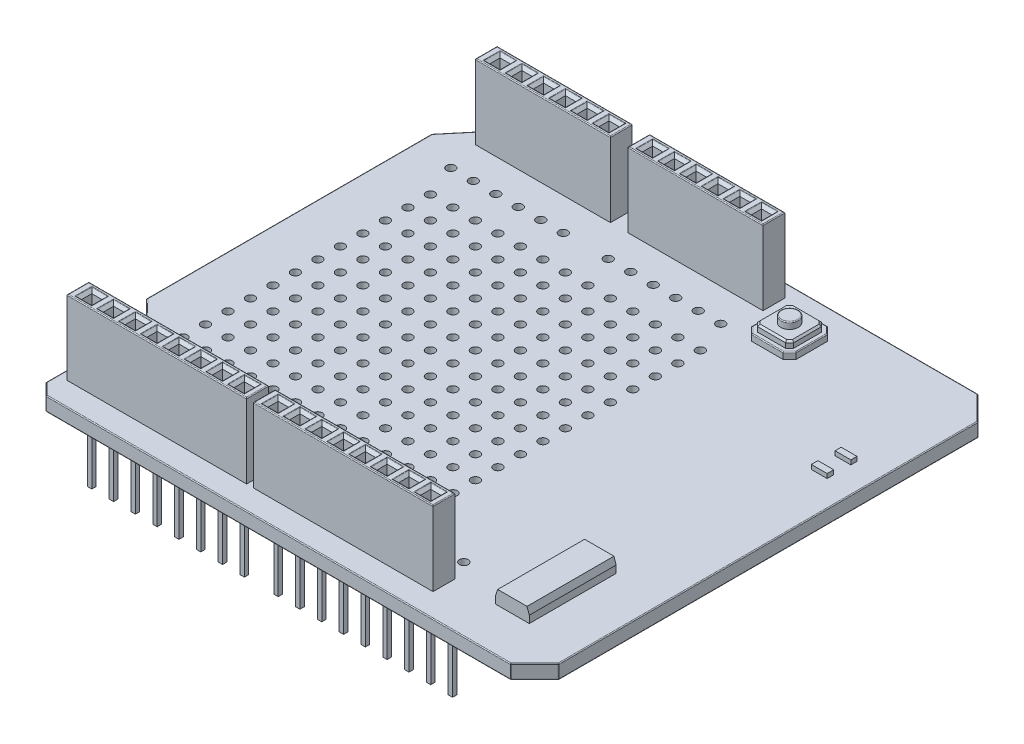
SolidWorks part; units mm, degrees
ref_plane "Front Plane" through (0, 0, 0) normal (0, 0, 1) x (1, 0, 0)
ref_plane "Top Plane" through (0, 0, 0) normal (0, 1, 0) x (1, 0, 0)
ref_plane "Right Plane" through (0, 0, 0) normal (1, 0, 0) x (0, 0, -1)
sketch "Sketch1" plane through (0, 0, 0) normal (0, 1, 0) x (1, 0, 0)
  line L1 (-29.955, 26.8) -> (29.955, 26.8)
  line L2 (-29.955, 26.8) -> (-29.955, -26.8)
  line L3 (-29.955, -26.8) -> (29.955, -26.8)
  line L4 (29.955, 26.8) -> (29.955, -26.8)
  line L5 (-29.955, 26.8) -> (29.955, -26.8) construction
  line L6 (-29.955, -26.8) -> (29.955, 26.8) construction
  point P0 (0, 0)
  dimension "D1" = 59.91
  dimension "D2" = 53.6
extrude "Boss-Extrude1" add sketch "Sketch1" along normal blind 1.63
sketch "Sketch2" plane through (0, 1.63, 0) normal (0, 1, 0) x (1, 0, 0)
  line L0 (29.955, 26.8) -> (-29.955, 26.8) construction
  line L1 (-26.385, 25.23) -> (-10.885, 25.23)
  line L2 (-26.385, 25.23) -> (-26.385, 22.73)
  line L3 (-26.385, 22.73) -> (-10.885, 22.73)
  line L4 (-10.885, 25.23) -> (-10.885, 22.73)
  line L5 (-26.385, 25.23) -> (-10.885, 22.73) construction
  line L6 (-26.385, 22.73) -> (-10.885, 25.23) construction
  line L7 (-29.955, 26.8) -> (-29.955, -26.8) construction
  line L8 (-8.885, 25.23) -> (-8.885, 22.73)
  line L9 (-8.885, 25.23) -> (6.615, 25.23)
  line L10 (6.615, 25.23) -> (6.615, 22.73)
  line L11 (-8.885, 22.73) -> (6.615, 22.73)
  line L12 (-26.385, 25.23) -> (-8.885, 25.23) construction
  line L13 (15.595, -21.5984) -> (15.595, -24.0984)
  line L14 (-26.385, -21.5984) -> (-5.785, -21.5984)
  line L15 (-26.385, -21.5984) -> (-26.385, -24.0984)
  line L16 (-26.385, -24.0984) -> (-5.785, -24.0984)
  line L17 (-5.785, -21.5984) -> (-5.785, -24.0984)
  line L18 (-26.385, -21.5984) -> (-5.785, -24.0984) construction
  line L19 (-26.385, -24.0984) -> (-5.785, -21.5984) construction
  line L20 (-5.005, -21.5984) -> (15.595, -21.5984)
  line L21 (-5.005, -24.0984) -> (15.595, -24.0984)
  line L22 (-5.005, -21.5984) -> (-5.005, -24.0984)
  point P0 (-18.635, 23.98)
  point P9 (-16.085, -22.8484)
  dimension "D1" = 15.5
  dimension "D2" = 2.5
  dimension "D3" = 1.57
  dimension "D4" = 3.57
  dimension "D6" = 17.5
  dimension "D7" = 2.5
  dimension "D8" = 20.6
  dimension "D9" = 3.57
  dimension "D10" = 2
  dimension "D5" = 2
extrude "Boss-Extrude2" add sketch "Sketch2" along normal blind 8.54
sketch "Sketch3" plane through (0, 1.63, 0) normal (0, 1, 0) x (1, 0, 0)
  line L0 (29.955, 26.8) -> (-29.955, 26.8) construction
  line L1 (8.995, 24.15) -> (12.605, 24.15)
  line L2 (8.245, 23.4) -> (8.245, 19.79)
  line L3 (8.995, 19.04) -> (12.605, 19.04)
  line L4 (13.355, 23.4) -> (13.355, 19.79)
  line L5 (8.245, 24.15) -> (13.355, 19.04) construction
  line L6 (8.245, 19.04) -> (13.355, 24.15) construction
  line L7 (29.955, -26.8) -> (29.955, 26.8) construction
  line L8 (12.605, 24.15) -> (13.355, 23.4)
  line L9 (8.245, 23.4) -> (8.995, 24.15)
  line L10 (8.245, 19.79) -> (8.995, 19.04)
  line L11 (12.605, 19.04) -> (13.355, 19.79)
  point P0 (10.8, 21.595)
  dimension "D1" = 5.11
  dimension "D2" = 5.11
  dimension "D3" = 2.65
  dimension "D4" = 16.6
  dimension "D5" = 0.75
  dimension "D6" = 45
  dimension "D7" = 0.75
  dimension "D8" = 45
  dimension "D9" = 0.75
  dimension "D10" = 45
  dimension "D11" = 0.75
  dimension "D12" = 45
extrude "Boss-Extrude3" add sketch "Sketch3" along normal blind 0.75
sketch "Sketch4" plane through (0, 2.38, 0) normal (0, 1, 0) x (1, 0, 0)
  line L47 (8.745, 19.9971) -> (9.3486, 19.3936)
  line L48 (8.745, 23.1929) -> (8.745, 19.9971)
  line L49 (9.2021, 23.65) -> (8.745, 23.1929)
  line L50 (12.605, 23.65) -> (9.2021, 23.65)
  line L51 (8.745, 19.9971) -> (9.2021, 19.54)
  line L52 (8.745, 23.1929) -> (8.745, 19.9971)
  line L53 (9.2021, 23.65) -> (8.745, 23.1929)
  line L54 (12.3979, 23.65) -> (9.2021, 23.65)
  line L65 (12.855, 23.1929) -> (12.2514, 23.7964)
  line L66 (12.855, 19.9971) -> (12.855, 23.1929)
  line L67 (12.3979, 19.54) -> (12.855, 19.9971)
  line L68 (8.995, 19.54) -> (12.3979, 19.54)
  line L69 (12.855, 23.1929) -> (12.3979, 23.65)
  line L70 (12.855, 19.9971) -> (12.855, 23.1929)
  line L71 (12.3979, 19.54) -> (12.855, 19.9971)
  line L72 (9.2021, 19.54) -> (12.3979, 19.54)
  dimension "D1" = 0.5
  dimension "D2" = 0.5
extrude "Boss-Extrude4" add sketch "Sketch4" along normal blind 0.75
sketch "Sketch5" plane through (0, 3.13, 0) normal (0, 1, 0) x (1, 0, 0)
  circle A0 centre (10.8, 21.595) radius 1
  dimension "D1" = 2
extrude "Boss-Extrude5" add sketch "Sketch5" along normal blind 0.75
chamfer "Chamfer1" distance 0.2 angle 45 8 edges at (8.9736, 3.13, -23.4214) (10.8, 3.13, -23.65) (12.6264, 3.13, -23.4214) (8.745, 3.13, -21.595) (8.9736, 3.13, -19.7686) (10.8, 3.13, -19.54) (12.6264, 3.13, -19.7686) (12.855, 3.13, -21.595)
fillet "Fillet1" radius 0.1 1 edges at (10.8, 3.88, -20.595)
fillet "Fillet2" radius 0.1 8 edges at (8.62, 2.38, -19.415) (8.245, 2.38, -21.595) (8.62, 2.38, -23.775) (10.8, 2.38, -24.15) (12.98, 2.38, -23.775) (10.8, 2.38, -19.04) (12.98, 2.38, -19.415) (13.355, 2.38, -21.595)
sketch "Sketch6" plane through (0, 1.63, 0) normal (0, 1, 0) x (1, 0, 0)
  line L0 (29.955, -26.8) -> (29.955, 26.8) construction
  line L1 (20.405, -11.78) -> (24.285, -11.78)
  line L2 (20.405, -11.78) -> (20.405, -21.75)
  line L3 (20.405, -21.75) -> (24.285, -21.75)
  line L4 (24.285, -11.78) -> (24.285, -21.75)
  line L5 (20.405, -11.78) -> (24.285, -21.75) construction
  line L6 (20.405, -21.75) -> (24.285, -11.78) construction
  line L7 (-29.955, -26.8) -> (29.955, -26.8) construction
  point P0 (22.345, -16.765)
  dimension "D1" = 3.88
  dimension "D2" = 9.97
  dimension "D3" = 5.67
  dimension "D4" = 5.05
extrude "Boss-Extrude6" add sketch "Sketch6" along normal blind 1.58
chamfer "Chamfer2" distance 0.75 angle 19 2 edges at (20.405, 3.21, 16.765) (24.285, 3.21, 16.765) first distance on face at (20.405, 2.42, 16.765) first distance on face at (24.285, 2.42, 16.765)
sketch "Sketch7" plane through (0, 10.17, 0) normal (0, 1, 0) x (1, 0, 0)
  line L0 (-26.385, 25.23) -> (-26.385, 22.73) construction
  line L1 (-25.385, 24.57) -> (-24.205, 24.57)
  line L2 (-25.385, 24.57) -> (-25.385, 23.39)
  line L3 (-25.385, 23.39) -> (-24.205, 23.39)
  line L4 (-24.205, 24.57) -> (-24.205, 23.39)
  line L5 (-25.385, 24.57) -> (-24.205, 23.39) construction
  line L6 (-25.385, 23.39) -> (-24.205, 24.57) construction
  line L7 (-26.385, 23.98) -> (-25.385, 23.98) construction
  line L8 (-22.885, 24.57) -> (-22.885, 23.39)
  line L9 (-22.885, 24.57) -> (-21.705, 24.57)
  line L10 (-21.705, 24.57) -> (-21.705, 23.39)
  line L11 (-22.885, 23.39) -> (-21.705, 23.39)
  line L12 (-20.385, 24.57) -> (-20.385, 23.39)
  line L13 (-20.385, 24.57) -> (-19.205, 24.57)
  line L14 (-19.205, 24.57) -> (-19.205, 23.39)
  line L15 (-20.385, 23.39) -> (-19.205, 23.39)
  line L16 (-17.885, 24.57) -> (-17.885, 23.39)
  line L17 (-17.885, 24.57) -> (-16.705, 24.57)
  line L18 (-16.705, 24.57) -> (-16.705, 23.39)
  line L19 (-17.885, 23.39) -> (-16.705, 23.39)
  line L20 (-15.385, 24.57) -> (-15.385, 23.39)
  line L21 (-15.385, 24.57) -> (-14.205, 24.57)
  line L22 (-14.205, 24.57) -> (-14.205, 23.39)
  line L23 (-15.385, 23.39) -> (-14.205, 23.39)
  line L24 (-12.885, 24.57) -> (-12.885, 23.39)
  line L25 (-12.885, 24.57) -> (-11.705, 24.57)
  line L26 (-11.705, 24.57) -> (-11.705, 23.39)
  line L27 (-12.885, 23.39) -> (-11.705, 23.39)
  line L28 (-26.385, -21.5984) -> (-26.385, -24.0984) construction
  line L29 (-25.385, -22.2584) -> (-24.205, -22.2584)
  line L30 (-25.385, -22.2584) -> (-25.385, -23.4384)
  line L31 (-25.385, -23.4384) -> (-24.205, -23.4384)
  line L32 (-7.885, 24.57) -> (-7.885, 23.39)
  line L33 (-7.885, 24.57) -> (-6.705, 24.57)
  line L34 (-6.705, 24.57) -> (-6.705, 23.39)
  line L35 (-7.885, 23.39) -> (-6.705, 23.39)
  line L36 (-5.385, 24.57) -> (-5.385, 23.39)
  line L37 (-5.385, 24.57) -> (-4.205, 24.57)
  line L38 (-4.205, 24.57) -> (-4.205, 23.39)
  line L39 (-5.385, 23.39) -> (-4.205, 23.39)
  line L40 (-2.885, 24.57) -> (-2.885, 23.39)
  line L41 (-2.885, 24.57) -> (-1.705, 24.57)
  line L42 (-1.705, 24.57) -> (-1.705, 23.39)
  line L43 (-2.885, 23.39) -> (-1.705, 23.39)
  line L44 (-0.385, 24.57) -> (-0.385, 23.39)
  line L45 (-0.385, 24.57) -> (0.795, 24.57)
  line L46 (0.795, 24.57) -> (0.795, 23.39)
  line L47 (-0.385, 23.39) -> (0.795, 23.39)
  line L48 (2.115, 24.57) -> (2.115, 23.39)
  line L49 (2.115, 24.57) -> (3.295, 24.57)
  line L50 (3.295, 24.57) -> (3.295, 23.39)
  line L51 (2.115, 23.39) -> (3.295, 23.39)
  line L52 (4.615, 24.57) -> (4.615, 23.39)
  line L53 (4.615, 24.57) -> (5.795, 24.57)
  line L54 (5.795, 24.57) -> (5.795, 23.39)
  line L55 (4.615, 23.39) -> (5.795, 23.39)
  line L56 (-10.385, 24.57) -> (-9.205, 24.57)
  line L57 (-9.205, 24.57) -> (-9.205, 23.39)
  line L58 (-10.385, 23.39) -> (-9.205, 23.39)
  line L59 (-10.385, 24.57) -> (-10.385, 23.39)
  line L60 (-24.205, -22.2584) -> (-24.205, -23.4384)
  line L61 (-25.385, -22.2584) -> (-24.205, -23.4384) construction
  line L62 (-25.385, -23.4384) -> (-24.205, -22.2584) construction
  line L63 (-26.385, -22.8484) -> (-25.385, -22.8484) construction
  line L64 (-26.385, -21.5984) -> (-26.385, -24.0984) construction
  line L65 (-21.705, -22.2584) -> (-21.705, -23.4384)
  line L66 (-22.885, -22.2584) -> (-21.705, -22.2584)
  line L67 (-22.885, -23.4384) -> (-21.705, -23.4384)
  line L68 (-22.885, -22.2584) -> (-22.885, -23.4384)
  line L69 (-19.205, -22.2584) -> (-19.205, -23.4384)
  line L70 (-20.385, -22.2584) -> (-19.205, -22.2584)
  line L71 (-20.385, -23.4384) -> (-19.205, -23.4384)
  line L72 (-20.385, -22.2584) -> (-20.385, -23.4384)
  line L73 (-16.705, -22.2584) -> (-16.705, -23.4384)
  line L74 (-17.885, -22.2584) -> (-16.705, -22.2584)
  line L75 (-17.885, -23.4384) -> (-16.705, -23.4384)
  line L76 (-17.885, -22.2584) -> (-17.885, -23.4384)
  line L77 (-14.205, -22.2584) -> (-14.205, -23.4384)
  line L78 (-15.385, -22.2584) -> (-14.205, -22.2584)
  line L79 (-15.385, -23.4384) -> (-14.205, -23.4384)
  line L80 (-15.385, -22.2584) -> (-15.385, -23.4384)
  line L81 (-11.705, -22.2584) -> (-11.705, -23.4384)
  line L82 (-12.885, -22.2584) -> (-11.705, -22.2584)
  line L83 (-12.885, -23.4384) -> (-11.705, -23.4384)
  line L84 (-12.885, -22.2584) -> (-12.885, -23.4384)
  line L85 (-9.205, -22.2584) -> (-9.205, -23.4384)
  line L86 (-10.385, -22.2584) -> (-9.205, -22.2584)
  line L87 (-10.385, -23.4384) -> (-9.205, -23.4384)
  line L88 (-10.385, -22.2584) -> (-10.385, -23.4384)
  line L89 (-6.705, -22.2584) -> (-6.705, -23.4384)
  line L90 (-7.885, -22.2584) -> (-6.705, -22.2584)
  line L91 (-7.885, -23.4384) -> (-6.705, -23.4384)
  line L92 (-7.885, -22.2584) -> (-7.885, -23.4384)
  line L93 (-5.005, -21.5984) -> (-5.005, -24.0984) construction
  line L94 (-4.005, -22.2584) -> (-2.825, -22.2584)
  line L95 (-4.005, -22.2584) -> (-4.005, -23.4384)
  line L96 (-4.005, -23.4384) -> (-2.825, -23.4384)
  line L97 (-2.825, -22.2584) -> (-2.825, -23.4384)
  line L98 (-4.005, -22.2584) -> (-2.825, -23.4384) construction
  line L99 (-4.005, -23.4384) -> (-2.825, -22.2584) construction
  line L100 (-4.005, -22.8484) -> (-5.005, -22.8484) construction
  line L101 (-5.005, -21.5984) -> (-5.005, -24.0984) construction
  line L102 (-1.505, -22.8484) -> (-2.505, -22.8484) construction
  line L103 (-0.325, -22.2584) -> (-0.325, -23.4384)
  line L104 (-1.505, -22.2584) -> (-0.325, -22.2584)
  line L105 (-1.505, -23.4384) -> (-0.325, -23.4384)
  line L106 (-1.505, -22.2584) -> (-1.505, -23.4384)
  line L107 (0.995, -22.8484) -> (-0.005, -22.8484) construction
  line L108 (2.175, -22.2584) -> (2.175, -23.4384)
  line L109 (0.995, -22.2584) -> (2.175, -22.2584)
  line L110 (0.995, -23.4384) -> (2.175, -23.4384)
  line L111 (0.995, -22.2584) -> (0.995, -23.4384)
  line L112 (3.495, -22.8484) -> (2.495, -22.8484) construction
  line L113 (4.675, -22.2584) -> (4.675, -23.4384)
  line L114 (3.495, -22.2584) -> (4.675, -22.2584)
  line L115 (3.495, -23.4384) -> (4.675, -23.4384)
  line L116 (3.495, -22.2584) -> (3.495, -23.4384)
  line L117 (5.995, -22.8484) -> (4.995, -22.8484) construction
  line L118 (7.175, -22.2584) -> (7.175, -23.4384)
  line L119 (5.995, -22.2584) -> (7.175, -22.2584)
  line L120 (5.995, -23.4384) -> (7.175, -23.4384)
  line L121 (5.995, -22.2584) -> (5.995, -23.4384)
  line L122 (8.495, -22.8484) -> (7.495, -22.8484) construction
  line L123 (9.675, -22.2584) -> (9.675, -23.4384)
  line L124 (8.495, -22.2584) -> (9.675, -22.2584)
  line L125 (8.495, -23.4384) -> (9.675, -23.4384)
  line L126 (8.495, -22.2584) -> (8.495, -23.4384)
  line L127 (10.995, -22.8484) -> (9.995, -22.8484) construction
  line L128 (12.175, -22.2584) -> (12.175, -23.4384)
  line L129 (10.995, -22.2584) -> (12.175, -22.2584)
  line L130 (10.995, -23.4384) -> (12.175, -23.4384)
  line L131 (10.995, -22.2584) -> (10.995, -23.4384)
  line L132 (13.495, -22.8484) -> (12.495, -22.8484) construction
  line L133 (14.675, -22.2584) -> (14.675, -23.4384)
  line L134 (13.495, -22.2584) -> (14.675, -22.2584)
  line L135 (13.495, -23.4384) -> (14.675, -23.4384)
  line L136 (13.495, -22.2584) -> (13.495, -23.4384)
  line L137 (-4.005, -22.8484) -> (-1.505, -22.8484) construction
  point P0 (-24.795, 23.98)
  point P5 (-26.385, 23.98)
  point P10 (-24.795, -22.8484)
  point P73 (-3.415, -22.8484)
  dimension "D1" = 1.18
  dimension "D2" = 1.18
  dimension "D3" = 1
  dimension "D5" = 1.18
  dimension "D6" = 1.18
  dimension "D7" = 1
  dimension "D9" = 1.18
  dimension "D10" = 1.18
  dimension "D11" = 1
  dimension "D13" = 2.5
  dimension "D4" = 13
  dimension "D8" = 8
  dimension "D12" = 8
extrude "Cut-Extrude1" cut sketch "Sketch7" against normal blind 6.58
chamfer "Chamfer3" distance 0.35 angle 45 112 edges at (-24.795, 10.17, -23.39) (-24.205, 10.17, -23.98) (-25.385, 10.17, -23.98) (-24.795, 10.17, -24.57) (14.085, 10.17, 23.4384) (14.675, 10.17, 22.8484) (13.495, 10.17, 22.8484) (14.085, 10.17, 22.2584) (11.585, 10.17, 23.4384) (12.175, 10.17, 22.8484) (10.995, 10.17, 22.8484) (11.585, 10.17, 22.2584) (9.085, 10.17, 23.4384) (9.675, 10.17, 22.8484) (8.495, 10.17, 22.8484) (9.085, 10.17, 22.2584) (6.585, 10.17, 23.4384) (7.175, 10.17, 22.8484) (5.995, 10.17, 22.8484) (6.585, 10.17, 22.2584) (4.085, 10.17, 23.4384) (4.675, 10.17, 22.8484) (3.495, 10.17, 22.8484) (4.085, 10.17, 22.2584) (1.585, 10.17, 23.4384) (2.175, 10.17, 22.8484) (0.995, 10.17, 22.8484) (1.585, 10.17, 22.2584) (-0.915, 10.17, 23.4384) (-0.325, 10.17, 22.8484) (-1.505, 10.17, 22.8484) (-0.915, 10.17, 22.2584) (-3.415, 10.17, 23.4384) (-2.825, 10.17, 22.8484) (-4.005, 10.17, 22.8484) (-3.415, 10.17, 22.2584) (-7.295, 10.17, 23.4384) (-7.885, 10.17, 22.8484) (-6.705, 10.17, 22.8484) (-7.295, 10.17, 22.2584) (-9.795, 10.17, 23.4384) (-10.385, 10.17, 22.8484) (-9.205, 10.17, 22.8484) (-9.795, 10.17, 22.2584) (-12.295, 10.17, 23.4384) (-12.885, 10.17, 22.8484) (-11.705, 10.17, 22.8484) (-12.295, 10.17, 22.2584) (-14.795, 10.17, 23.4384) (-15.385, 10.17, 22.8484) (-14.205, 10.17, 22.8484) (-14.795, 10.17, 22.2584) (-17.295, 10.17, 23.4384) (-17.885, 10.17, 22.8484) (-16.705, 10.17, 22.8484) (-17.295, 10.17, 22.2584) (-19.795, 10.17, 23.4384) (-20.385, 10.17, 22.8484) (-19.205, 10.17, 22.8484) (-19.795, 10.17, 22.2584) (-22.295, 10.17, 23.4384) (-22.885, 10.17, 22.8484) (-21.705, 10.17, 22.8484) (-22.295, 10.17, 22.2584) (-24.795, 10.17, 23.4384) (-25.385, 10.17, 22.8484) (-24.205, 10.17, 22.8484) (-24.795, 10.17, 22.2584) (5.205, 10.17, -24.57) (4.615, 10.17, -23.98) (5.795, 10.17, -23.98) (5.205, 10.17, -23.39) (2.705, 10.17, -24.57) (2.115, 10.17, -23.98) (3.295, 10.17, -23.98) (2.705, 10.17, -23.39) (0.205, 10.17, -24.57) (-0.385, 10.17, -23.98) (0.795, 10.17, -23.98) (0.205, 10.17, -23.39) (-2.295, 10.17, -24.57) (-2.885, 10.17, -23.98) (-1.705, 10.17, -23.98) (-2.295, 10.17, -23.39) (-4.795, 10.17, -24.57) (-5.385, 10.17, -23.98) (-4.205, 10.17, -23.98) (-4.795, 10.17, -23.39) (-7.295, 10.17, -24.57) (-7.885, 10.17, -23.98) (-6.705, 10.17, -23.98) (-7.295, 10.17, -23.39) (-12.295, 10.17, -23.39) (-12.885, 10.17, -23.98) (-12.295, 10.17, -24.57) (-11.705, 10.17, -23.98) (-15.385, 10.17, -23.98) (-14.795, 10.17, -24.57) (-14.205, 10.17, -23.98) (-14.795, 10.17, -23.39) (-17.885, 10.17, -23.98) (-17.295, 10.17, -24.57) (-16.705, 10.17, -23.98) (-17.295, 10.17, -23.39) (-20.385, 10.17, -23.98) (-19.795, 10.17, -24.57) (-19.205, 10.17, -23.98) (-19.795, 10.17, -23.39) (-22.295, 10.17, -23.39) (-21.705, 10.17, -23.98) (-22.885, 10.17, -23.98) (-22.295, 10.17, -24.57)
chamfer "Chamfer4" distance 2.75 angle 45 2 edges at (29.955, 0.815, 26.8) (29.955, 0.815, -26.8)
sketch "Sketch8" plane through (0, 1.63, 0) normal (0, 1, 0) x (1, 0, 0)
  line L0 (-27.415, 26.8) -> (-27.415, 24.34)
  line L1 (27.205, 26.8) -> (-29.955, 26.8) construction
  line L2 (-29.955, -26.8) -> (27.205, -26.8) construction
  line L3 (-29.955, 26.8) -> (-29.955, -26.8) construction
  line L4 (-27.415, -14) -> (-27.415, -26.8)
  line L5 (-27.415, 26.8) -> (-29.955, 26.8)
  line L6 (-27.415, 24.34) -> (-29.955, 21.3)
  line L7 (-29.955, -11.4) -> (-27.415, -14)
  line L8 (-29.955, 26.8) -> (-29.955, 21.3)
  line L9 (-27.415, -26.8) -> (-29.955, -26.8)
  line L10 (-29.955, -26.8) -> (-29.955, -11.4)
  dimension "D1" = 2.54
extrude "Cut-Extrude2" cut sketch "Sketch8" against normal through all
chamfer "Chamfer5" distance 1.32 angle 45 1 edges at (-27.415, 0.815, 26.8)
sketch "Sketch9" plane through (0, 1.63, 0) normal (0, 1, 0) x (1, 0, 0)
  line L0 (27.205, 26.8) -> (-27.415, 26.8) construction
  line L1 (29.955, -24.05) -> (29.955, 24.05) construction
  line L2 (6.955, 15.2) -> (4.375, 15.2) construction
  line L3 (-7.4135, 19.0059) -> (-4.8335, 19.0059) construction
  line L4 (-25.4699, -19.4032) -> (-22.8899, -19.4032) construction
  line L5 (-3.6313, -19.4032) -> (-1.0513, -19.4032) construction
  circle A0 centre (6.955, 15.2) radius 0.5
  circle A1 centre (4.375, 15.2) radius 0.5
  circle A2 centre (1.795, 15.2) radius 0.5
  circle A3 centre (-0.785, 15.2) radius 0.5
  circle A4 centre (-3.365, 15.2) radius 0.5
  circle A5 centre (-5.945, 15.2) radius 0.5
  circle A6 centre (-8.525, 15.2) radius 0.5
  circle A7 centre (-11.105, 15.2) radius 0.5
  circle A8 centre (-13.685, 15.2) radius 0.5
  circle A9 centre (-16.265, 15.2) radius 0.5
  circle A10 centre (-18.845, 15.2) radius 0.5
  circle A11 centre (-21.425, 15.2) radius 0.5
  circle A12 centre (-24.005, 15.2) radius 0.5
  circle A13 centre (6.955, 12.62) radius 0.5
  circle A14 centre (4.375, 12.62) radius 0.5
  circle A15 centre (1.795, 12.62) radius 0.5
  circle A16 centre (-0.785, 12.62) radius 0.5
  circle A17 centre (-3.365, 12.62) radius 0.5
  circle A18 centre (-5.945, 12.62) radius 0.5
  circle A19 centre (-8.525, 12.62) radius 0.5
  circle A20 centre (-11.105, 12.62) radius 0.5
  circle A21 centre (-13.685, 12.62) radius 0.5
  circle A22 centre (-16.265, 12.62) radius 0.5
  circle A23 centre (-18.845, 12.62) radius 0.5
  circle A24 centre (-21.425, 12.62) radius 0.5
  circle A25 centre (-24.005, 12.62) radius 0.5
  circle A26 centre (6.955, 10.04) radius 0.5
  circle A27 centre (4.375, 10.04) radius 0.5
  circle A28 centre (1.795, 10.04) radius 0.5
  circle A29 centre (-0.785, 10.04) radius 0.5
  circle A30 centre (-3.365, 10.04) radius 0.5
  circle A31 centre (-5.945, 10.04) radius 0.5
  circle A32 centre (-8.525, 10.04) radius 0.5
  circle A33 centre (-11.105, 10.04) radius 0.5
  circle A34 centre (-13.685, 10.04) radius 0.5
  circle A35 centre (-16.265, 10.04) radius 0.5
  circle A36 centre (-18.845, 10.04) radius 0.5
  circle A37 centre (-21.425, 10.04) radius 0.5
  circle A38 centre (-24.005, 10.04) radius 0.5
  circle A39 centre (6.955, 7.46) radius 0.5
  circle A40 centre (4.375, 7.46) radius 0.5
  circle A41 centre (1.795, 7.46) radius 0.5
  circle A42 centre (-0.785, 7.46) radius 0.5
  circle A43 centre (-3.365, 7.46) radius 0.5
  circle A44 centre (-5.945, 7.46) radius 0.5
  circle A45 centre (-8.525, 7.46) radius 0.5
  circle A46 centre (-11.105, 7.46) radius 0.5
  circle A47 centre (-13.685, 7.46) radius 0.5
  circle A48 centre (-16.265, 7.46) radius 0.5
  circle A49 centre (-18.845, 7.46) radius 0.5
  circle A50 centre (-21.425, 7.46) radius 0.5
  circle A51 centre (-24.005, 7.46) radius 0.5
  circle A52 centre (6.955, 4.88) radius 0.5
  circle A53 centre (4.375, 4.88) radius 0.5
  circle A54 centre (1.795, 4.88) radius 0.5
  circle A55 centre (-0.785, 4.88) radius 0.5
  circle A56 centre (-3.365, 4.88) radius 0.5
  circle A57 centre (-5.945, 4.88) radius 0.5
  circle A58 centre (-8.525, 4.88) radius 0.5
  circle A59 centre (-11.105, 4.88) radius 0.5
  circle A60 centre (-13.685, 4.88) radius 0.5
  circle A61 centre (-16.265, 4.88) radius 0.5
  circle A62 centre (-18.845, 4.88) radius 0.5
  circle A63 centre (-21.425, 4.88) radius 0.5
  circle A64 centre (-24.005, 4.88) radius 0.5
  circle A65 centre (6.955, 2.3) radius 0.5
  circle A66 centre (4.375, 2.3) radius 0.5
  circle A67 centre (1.795, 2.3) radius 0.5
  circle A68 centre (-0.785, 2.3) radius 0.5
  circle A69 centre (-3.365, 2.3) radius 0.5
  circle A70 centre (-5.945, 2.3) radius 0.5
  circle A71 centre (-8.525, 2.3) radius 0.5
  circle A72 centre (-11.105, 2.3) radius 0.5
  circle A73 centre (-13.685, 2.3) radius 0.5
  circle A74 centre (-16.265, 2.3) radius 0.5
  circle A75 centre (-18.845, 2.3) radius 0.5
  circle A76 centre (-21.425, 2.3) radius 0.5
  circle A77 centre (-24.005, 2.3) radius 0.5
  circle A78 centre (6.955, -0.28) radius 0.5
  circle A79 centre (4.375, -0.28) radius 0.5
  circle A80 centre (1.795, -0.28) radius 0.5
  circle A81 centre (-0.785, -0.28) radius 0.5
  circle A82 centre (-3.365, -0.28) radius 0.5
  circle A83 centre (-5.945, -0.28) radius 0.5
  circle A84 centre (-8.525, -0.28) radius 0.5
  circle A85 centre (-11.105, -0.28) radius 0.5
  circle A86 centre (-13.685, -0.28) radius 0.5
  circle A87 centre (-16.265, -0.28) radius 0.5
  circle A88 centre (-18.845, -0.28) radius 0.5
  circle A89 centre (-21.425, -0.28) radius 0.5
  circle A90 centre (-24.005, -0.28) radius 0.5
  circle A91 centre (6.955, -2.86) radius 0.5
  circle A92 centre (4.375, -2.86) radius 0.5
  circle A93 centre (1.795, -2.86) radius 0.5
  circle A94 centre (-0.785, -2.86) radius 0.5
  circle A95 centre (-3.365, -2.86) radius 0.5
  circle A96 centre (-5.945, -2.86) radius 0.5
  circle A97 centre (-8.525, -2.86) radius 0.5
  circle A98 centre (-11.105, -2.86) radius 0.5
  circle A99 centre (-13.685, -2.86) radius 0.5
  circle A100 centre (-16.265, -2.86) radius 0.5
  circle A101 centre (-18.845, -2.86) radius 0.5
  circle A102 centre (-21.425, -2.86) radius 0.5
  circle A103 centre (-24.005, -2.86) radius 0.5
  circle A104 centre (6.955, -5.44) radius 0.5
  circle A105 centre (4.375, -5.44) radius 0.5
  circle A106 centre (1.795, -5.44) radius 0.5
  circle A107 centre (-0.785, -5.44) radius 0.5
  circle A108 centre (-3.365, -5.44) radius 0.5
  circle A109 centre (-5.945, -5.44) radius 0.5
  circle A110 centre (-8.525, -5.44) radius 0.5
  circle A111 centre (-11.105, -5.44) radius 0.5
  circle A112 centre (-13.685, -5.44) radius 0.5
  circle A113 centre (-16.265, -5.44) radius 0.5
  circle A114 centre (-18.845, -5.44) radius 0.5
  circle A115 centre (-21.425, -5.44) radius 0.5
  circle A116 centre (-24.005, -5.44) radius 0.5
  circle A117 centre (6.955, -8.02) radius 0.5
  circle A118 centre (4.375, -8.02) radius 0.5
  circle A119 centre (1.795, -8.02) radius 0.5
  circle A120 centre (-0.785, -8.02) radius 0.5
  circle A121 centre (-3.365, -8.02) radius 0.5
  circle A122 centre (-5.945, -8.02) radius 0.5
  circle A123 centre (-8.525, -8.02) radius 0.5
  circle A124 centre (-11.105, -8.02) radius 0.5
  circle A125 centre (-13.685, -8.02) radius 0.5
  circle A126 centre (-16.265, -8.02) radius 0.5
  circle A127 centre (-18.845, -8.02) radius 0.5
  circle A128 centre (-21.425, -8.02) radius 0.5
  circle A129 centre (-24.005, -8.02) radius 0.5
  circle A130 centre (6.955, -10.6) radius 0.5
  circle A131 centre (4.375, -10.6) radius 0.5
  circle A132 centre (1.795, -10.6) radius 0.5
  circle A133 centre (-0.785, -10.6) radius 0.5
  circle A134 centre (-3.365, -10.6) radius 0.5
  circle A135 centre (-5.945, -10.6) radius 0.5
  circle A136 centre (-8.525, -10.6) radius 0.5
  circle A137 centre (-11.105, -10.6) radius 0.5
  circle A138 centre (-13.685, -10.6) radius 0.5
  circle A139 centre (-16.265, -10.6) radius 0.5
  circle A140 centre (-18.845, -10.6) radius 0.5
  circle A141 centre (-21.425, -10.6) radius 0.5
  circle A142 centre (-24.005, -10.6) radius 0.5
  circle A143 centre (6.955, -13.18) radius 0.5
  circle A144 centre (4.375, -13.18) radius 0.5
  circle A145 centre (1.795, -13.18) radius 0.5
  circle A146 centre (-0.785, -13.18) radius 0.5
  circle A147 centre (-3.365, -13.18) radius 0.5
  circle A148 centre (-5.945, -13.18) radius 0.5
  circle A149 centre (-8.525, -13.18) radius 0.5
  circle A150 centre (-11.105, -13.18) radius 0.5
  circle A151 centre (-13.685, -13.18) radius 0.5
  circle A152 centre (-16.265, -13.18) radius 0.5
  circle A153 centre (-18.845, -13.18) radius 0.5
  circle A154 centre (-21.425, -13.18) radius 0.5
  circle A155 centre (-24.005, -13.18) radius 0.5
  circle A156 centre (6.955, -15.76) radius 0.5
  circle A157 centre (4.375, -15.76) radius 0.5
  circle A158 centre (1.795, -15.76) radius 0.5
  circle A159 centre (-0.785, -15.76) radius 0.5
  circle A160 centre (-3.365, -15.76) radius 0.5
  circle A161 centre (-5.945, -15.76) radius 0.5
  circle A162 centre (-8.525, -15.76) radius 0.5
  circle A163 centre (-11.105, -15.76) radius 0.5
  circle A164 centre (-13.685, -15.76) radius 0.5
  circle A165 centre (-16.265, -15.76) radius 0.5
  circle A166 centre (-18.845, -15.76) radius 0.5
  circle A167 centre (-21.425, -15.76) radius 0.5
  circle A168 centre (-24.005, -15.76) radius 0.5
  circle A169 centre (-25.4699, 19.0059) radius 0.5
  circle A170 centre (-22.8899, 19.0059) radius 0.5
  circle A171 centre (-20.3099, 19.0059) radius 0.5
  circle A172 centre (-17.7299, 19.0059) radius 0.5
  circle A173 centre (-15.1499, 19.0059) radius 0.5
  circle A174 centre (-12.5699, 19.0059) radius 0.5
  circle A175 centre (-7.4135, 19.0059) radius 0.5
  circle A176 centre (-4.8335, 19.0059) radius 0.5
  circle A177 centre (-2.2535, 19.0059) radius 0.5
  circle A178 centre (0.3265, 19.0059) radius 0.5
  circle A179 centre (2.9065, 19.0059) radius 0.5
  circle A180 centre (5.4865, 19.0059) radius 0.5
  circle A181 centre (-25.4699, -19.4032) radius 0.5
  circle A182 centre (-22.8899, -19.4032) radius 0.5
  circle A183 centre (-20.3099, -19.4032) radius 0.5
  circle A184 centre (-17.7299, -19.4032) radius 0.5
  circle A185 centre (-15.1499, -19.4032) radius 0.5
  circle A186 centre (-12.5699, -19.4032) radius 0.5
  circle A187 centre (-9.9899, -19.4032) radius 0.5
  circle A188 centre (-7.4099, -19.4032) radius 0.5
  circle A189 centre (-3.6313, -19.4032) radius 0.5
  circle A190 centre (-1.0513, -19.4032) radius 0.5
  circle A191 centre (1.5287, -19.4032) radius 0.5
  circle A192 centre (4.1087, -19.4032) radius 0.5
  circle A193 centre (6.6887, -19.4032) radius 0.5
  circle A194 centre (9.2687, -19.4032) radius 0.5
  circle A195 centre (11.8487, -19.4032) radius 0.5
  circle A196 centre (14.4287, -19.4032) radius 0.5
  dimension "D1" = 11.6
  dimension "D2" = 23
  dimension "D3" = 1
  dimension "D7" = 1
  dimension "D9" = 1
  dimension "D12" = 1
  dimension "D15" = 1
  dimension "D6" = 2.58
  dimension "D11" = 2.58
  dimension "D14" = 2.58
  dimension "D17" = 2.58
  dimension "D4" = 13
  dimension "D5" = 13
  dimension "D8" = 6
  dimension "D10" = 6
  dimension "D13" = 8
  dimension "D16" = 8
extrude "Cut-Extrude3" cut sketch "Sketch9" against normal through all
sketch "Sketch10" plane through (0, 1.63, 0) normal (0, 1, 0) x (1, 0, 0)
  line L1 (25.1543, 13.1559) -> (26.967, 13.1559)
  line L2 (25.1543, 13.1559) -> (25.1543, 12.4543)
  line L3 (25.1543, 12.4543) -> (26.967, 12.4543)
  line L4 (26.967, 13.1559) -> (26.967, 12.4543)
  line L5 (25.1543, 13.1559) -> (26.967, 12.4543) construction
  line L6 (25.1543, 12.4543) -> (26.967, 13.1559) construction
  line L7 (25.1543, 10.4906) -> (26.967, 10.4906)
  line L8 (25.1543, 10.4906) -> (25.1543, 9.7353)
  line L9 (25.1543, 9.7353) -> (26.967, 9.7353)
  line L10 (26.967, 10.4906) -> (26.967, 9.7353)
  line L11 (25.1543, 10.4906) -> (26.967, 9.7353) construction
  line L12 (25.1543, 9.7353) -> (26.967, 10.4906) construction
  point P0 (26.0606, 12.8051)
  point P5 (26.0606, 10.1129)
extrude "Boss-Extrude7" add sketch "Sketch10" along normal blind 0.5
sketch "Sketch11" plane through (0, 0, 0) normal (0, -1, 0) x (1, 0, 0)
  line L0 (-25.385, 23.4384) -> (-24.205, 22.2584) construction
  line L1 (-24.205, 23.4384) -> (-25.385, 22.2584) construction
  line L2 (-22.045, 23.0984) -> (-22.045, 22.5984)
  line L3 (-25.045, 23.0984) -> (-24.545, 23.0984)
  line L4 (-25.045, 23.0984) -> (-25.045, 22.5984)
  line L5 (-25.045, 22.5984) -> (-24.545, 22.5984)
  line L6 (-24.545, 23.0984) -> (-24.545, 22.5984)
  line L7 (-25.045, 23.0984) -> (-24.545, 22.5984) construction
  line L8 (-25.045, 22.5984) -> (-24.545, 23.0984) construction
  line L9 (-22.545, 22.5984) -> (-22.045, 22.5984)
  line L10 (-22.545, 23.0984) -> (-22.045, 23.0984)
  line L11 (-22.545, 23.0984) -> (-22.545, 22.5984)
  line L12 (-19.545, 23.0984) -> (-19.545, 22.5984)
  line L13 (-20.045, 22.5984) -> (-19.545, 22.5984)
  line L14 (-20.045, 23.0984) -> (-19.545, 23.0984)
  line L15 (-20.045, 23.0984) -> (-20.045, 22.5984)
  line L16 (-17.045, 23.0984) -> (-17.045, 22.5984)
  line L17 (-17.545, 22.5984) -> (-17.045, 22.5984)
  line L18 (-17.545, 23.0984) -> (-17.045, 23.0984)
  line L19 (-17.545, 23.0984) -> (-17.545, 22.5984)
  line L20 (-14.545, 23.0984) -> (-14.545, 22.5984)
  line L21 (-15.045, 22.5984) -> (-14.545, 22.5984)
  line L22 (-15.045, 23.0984) -> (-14.545, 23.0984)
  line L23 (-15.045, 23.0984) -> (-15.045, 22.5984)
  line L24 (-12.045, 23.0984) -> (-12.045, 22.5984)
  line L25 (-12.545, 22.5984) -> (-12.045, 22.5984)
  line L26 (-12.545, 23.0984) -> (-12.045, 23.0984)
  line L27 (-12.545, 23.0984) -> (-12.545, 22.5984)
  line L28 (-9.545, 23.0984) -> (-9.545, 22.5984)
  line L29 (-10.045, 22.5984) -> (-9.545, 22.5984)
  line L30 (-10.045, 23.0984) -> (-9.545, 23.0984)
  line L31 (-10.045, 23.0984) -> (-10.045, 22.5984)
  line L32 (-7.045, 23.0984) -> (-7.045, 22.5984)
  line L33 (-7.545, 22.5984) -> (-7.045, 22.5984)
  line L34 (-7.545, 23.0984) -> (-7.045, 23.0984)
  line L35 (-7.545, 23.0984) -> (-7.545, 22.5984)
  line L36 (-4.005, 23.4384) -> (-2.825, 22.2584) construction
  line L37 (-2.825, 23.4384) -> (-4.005, 22.2584) construction
  line L38 (-0.665, 23.0984) -> (-0.665, 22.5984)
  line L39 (-3.665, 23.0984) -> (-3.165, 23.0984)
  line L40 (-3.665, 23.0984) -> (-3.665, 22.5984)
  line L41 (-3.665, 22.5984) -> (-3.165, 22.5984)
  line L42 (-3.165, 23.0984) -> (-3.165, 22.5984)
  line L43 (-3.665, 23.0984) -> (-3.165, 22.5984) construction
  line L44 (-3.665, 22.5984) -> (-3.165, 23.0984) construction
  line L45 (-1.165, 23.0984) -> (-0.665, 23.0984)
  line L46 (-1.165, 22.5984) -> (-0.665, 22.5984)
  line L47 (-1.165, 23.0984) -> (-1.165, 22.5984)
  line L48 (1.835, 23.0984) -> (1.835, 22.5984)
  line L49 (1.335, 23.0984) -> (1.835, 23.0984)
  line L50 (1.335, 22.5984) -> (1.835, 22.5984)
  line L51 (1.335, 23.0984) -> (1.335, 22.5984)
  line L52 (4.335, 23.0984) -> (4.335, 22.5984)
  line L53 (3.835, 23.0984) -> (4.335, 23.0984)
  line L54 (3.835, 22.5984) -> (4.335, 22.5984)
  line L55 (3.835, 23.0984) -> (3.835, 22.5984)
  line L56 (6.835, 23.0984) -> (6.835, 22.5984)
  line L57 (6.335, 23.0984) -> (6.835, 23.0984)
  line L58 (6.335, 22.5984) -> (6.835, 22.5984)
  line L59 (6.335, 23.0984) -> (6.335, 22.5984)
  line L60 (9.335, 23.0984) -> (9.335, 22.5984)
  line L61 (8.835, 23.0984) -> (9.335, 23.0984)
  line L62 (8.835, 22.5984) -> (9.335, 22.5984)
  line L63 (8.835, 23.0984) -> (8.835, 22.5984)
  line L64 (11.835, 23.0984) -> (11.835, 22.5984)
  line L65 (11.335, 23.0984) -> (11.835, 23.0984)
  line L66 (11.335, 22.5984) -> (11.835, 22.5984)
  line L67 (11.335, 23.0984) -> (11.335, 22.5984)
  line L68 (14.335, 23.0984) -> (14.335, 22.5984)
  line L69 (13.835, 23.0984) -> (14.335, 23.0984)
  line L70 (13.835, 22.5984) -> (14.335, 22.5984)
  line L71 (13.835, 23.0984) -> (13.835, 22.5984)
  line L72 (16.835, 23.0984) -> (16.835, 22.5984)
  line L73 (16.335, 23.0984) -> (16.835, 23.0984)
  line L74 (16.335, 22.5984) -> (16.835, 22.5984)
  line L75 (16.335, 23.0984) -> (16.335, 22.5984)
  line L76 (-3.165, 23.0984) -> (-0.665, 23.0984) construction
  line L77 (-25.385, -23.39) -> (-24.205, -24.57) construction
  line L78 (-24.205, -23.39) -> (-25.385, -24.57) construction
  line L79 (-22.045, -23.73) -> (-22.045, -24.23)
  line L80 (-25.045, -23.73) -> (-24.545, -23.73)
  line L81 (-25.045, -23.73) -> (-25.045, -24.23)
  line L82 (-25.045, -24.23) -> (-24.545, -24.23)
  line L83 (-24.545, -23.73) -> (-24.545, -24.23)
  line L84 (-25.045, -23.73) -> (-24.545, -24.23) construction
  line L85 (-25.045, -24.23) -> (-24.545, -23.73) construction
  line L86 (-22.545, -23.73) -> (-22.045, -23.73)
  line L87 (-22.545, -24.23) -> (-22.045, -24.23)
  line L88 (-22.545, -23.73) -> (-22.545, -24.23)
  line L89 (-19.545, -23.73) -> (-19.545, -24.23)
  line L90 (-20.045, -23.73) -> (-19.545, -23.73)
  line L91 (-20.045, -24.23) -> (-19.545, -24.23)
  line L92 (-20.045, -23.73) -> (-20.045, -24.23)
  line L93 (-17.045, -23.73) -> (-17.045, -24.23)
  line L94 (-17.545, -23.73) -> (-17.045, -23.73)
  line L95 (-17.545, -24.23) -> (-17.045, -24.23)
  line L96 (-17.545, -23.73) -> (-17.545, -24.23)
  line L97 (-14.545, -23.73) -> (-14.545, -24.23)
  line L98 (-15.045, -23.73) -> (-14.545, -23.73)
  line L99 (-15.045, -24.23) -> (-14.545, -24.23)
  line L100 (-15.045, -23.73) -> (-15.045, -24.23)
  line L101 (-12.045, -23.73) -> (-12.045, -24.23)
  line L102 (-12.545, -23.73) -> (-12.045, -23.73)
  line L103 (-12.545, -24.23) -> (-12.045, -24.23)
  line L104 (-12.545, -23.73) -> (-12.545, -24.23)
  line L109 (-7.045, -23.73) -> (-7.045, -24.23)
  line L110 (-7.545, -23.73) -> (-7.045, -23.73)
  line L111 (-7.545, -24.23) -> (-7.045, -24.23)
  line L112 (-7.545, -23.73) -> (-7.545, -24.23)
  line L113 (-4.545, -23.73) -> (-4.545, -24.23)
  line L114 (-5.045, -23.73) -> (-4.545, -23.73)
  line L115 (-5.045, -24.23) -> (-4.545, -24.23)
  line L116 (-5.045, -23.73) -> (-5.045, -24.23)
  line L117 (-2.045, -23.73) -> (-2.045, -24.23)
  line L118 (-2.545, -23.73) -> (-2.045, -23.73)
  line L119 (-2.545, -24.23) -> (-2.045, -24.23)
  line L120 (-2.545, -23.73) -> (-2.545, -24.23)
  line L121 (0.455, -23.73) -> (0.455, -24.23)
  line L122 (-0.045, -23.73) -> (0.455, -23.73)
  line L123 (-0.045, -24.23) -> (0.455, -24.23)
  line L124 (-0.045, -23.73) -> (-0.045, -24.23)
  line L125 (2.955, -23.73) -> (2.955, -24.23)
  line L126 (2.455, -23.73) -> (2.955, -23.73)
  line L127 (2.455, -24.23) -> (2.955, -24.23)
  line L128 (2.455, -23.73) -> (2.455, -24.23)
  line L129 (5.455, -23.73) -> (5.455, -24.23)
  line L130 (4.955, -23.73) -> (5.455, -23.73)
  line L131 (4.955, -24.23) -> (5.455, -24.23)
  line L132 (4.955, -23.73) -> (4.955, -24.23)
  line L133 (-24.545, -23.73) -> (-22.045, -23.73) construction
  line L134 (-10.045, -23.73) -> (-9.545, -23.73)
  line L135 (-10.045, -23.73) -> (-10.045, -24.23)
  line L136 (-10.045, -24.23) -> (-9.545, -24.23)
  line L137 (-9.545, -23.73) -> (-9.545, -24.23)
  point P8 (-24.795, 22.8484)
  point P49 (-3.415, 22.8484)
  point P96 (-24.795, -23.98)
  dimension "D1" = 0.5
  dimension "D2" = 0.5
  dimension "D4" = 0.5
  dimension "D5" = 9
  dimension "D6" = 2.5
  dimension "D7" = 0.5
  dimension "D9" = 2.5
  dimension "D3" = 8
  dimension "D8" = 13
extrude "Boss-Extrude8" add sketch "Sketch11" along normal blind 8.75
fillet "Fillet5" radius 0.1 128 edges at (-8.885, 10.17, -23.98) (-1.135, 10.17, -25.23) (6.615, 10.17, -23.98) (-1.135, 10.17, -22.73) (-7.295, 10.17, -23.04) (-6.355, 10.17, -23.98) (-7.295, 10.17, -24.92) (-8.235, 10.17, -23.98) (-4.795, 10.17, -23.04) (-3.855, 10.17, -23.98) (-4.795, 10.17, -24.92) (-5.735, 10.17, -23.98) (-2.295, 10.17, -23.04) (-1.355, 10.17, -23.98) (-2.295, 10.17, -24.92) (-3.235, 10.17, -23.98) (0.205, 10.17, -23.04) (1.145, 10.17, -23.98) (0.205, 10.17, -24.92) (-0.735, 10.17, -23.98) (2.705, 10.17, -23.04) (3.645, 10.17, -23.98) (2.705, 10.17, -24.92) (1.765, 10.17, -23.98) (5.205, 10.17, -23.04) (6.145, 10.17, -23.98) (5.205, 10.17, -24.92) (4.265, 10.17, -23.98) (-18.635, 10.17, -22.73) (-26.385, 10.17, -23.98) (-18.635, 10.17, -25.23) (-10.885, 10.17, -23.98) (-24.795, 10.17, -24.92) (-25.735, 10.17, -23.98) (-24.795, 10.17, -23.04) (-23.855, 10.17, -23.98) (-22.295, 10.17, -24.92) (-23.235, 10.17, -23.98) (-22.295, 10.17, -23.04) (-21.355, 10.17, -23.98) (-18.855, 10.17, -23.98) (-19.795, 10.17, -24.92) (-20.735, 10.17, -23.98) (-19.795, 10.17, -23.04) (-16.355, 10.17, -23.98) (-17.295, 10.17, -24.92) (-18.235, 10.17, -23.98) (-17.295, 10.17, -23.04) (-13.855, 10.17, -23.98) (-14.795, 10.17, -24.92) (-15.735, 10.17, -23.98) (-14.795, 10.17, -23.04) (-12.295, 10.17, -24.92) (-13.235, 10.17, -23.98) (-12.295, 10.17, -23.04) (-11.355, 10.17, -23.98) (-3.415, 10.17, 21.9084) (-4.355, 10.17, 22.8484) (-3.415, 10.17, 23.7884) (-2.475, 10.17, 22.8484) (-0.915, 10.17, 21.9084) (-1.855, 10.17, 22.8484) (-0.915, 10.17, 23.7884) (0.025, 10.17, 22.8484) (1.585, 10.17, 21.9084) (0.645, 10.17, 22.8484) (1.585, 10.17, 23.7884) (2.525, 10.17, 22.8484) (4.085, 10.17, 21.9084) (3.145, 10.17, 22.8484) (4.085, 10.17, 23.7884) (5.025, 10.17, 22.8484) (6.585, 10.17, 21.9084) (5.645, 10.17, 22.8484) (6.585, 10.17, 23.7884) (7.525, 10.17, 22.8484) (9.085, 10.17, 21.9084) (8.145, 10.17, 22.8484) (9.085, 10.17, 23.7884) (10.025, 10.17, 22.8484) (11.585, 10.17, 21.9084) (10.645, 10.17, 22.8484) (11.585, 10.17, 23.7884) (12.525, 10.17, 22.8484) (14.085, 10.17, 21.9084) (13.145, 10.17, 22.8484) (14.085, 10.17, 23.7884) (15.025, 10.17, 22.8484) (-16.085, 10.17, 24.0984) (-26.385, 10.17, 22.8484) (-16.085, 10.17, 21.5984) (-5.785, 10.17, 22.8484) (-24.795, 10.17, 21.9084) (-25.735, 10.17, 22.8484) (-24.795, 10.17, 23.7884) (-23.855, 10.17, 22.8484) (-22.295, 10.17, 21.9084) (-23.235, 10.17, 22.8484) (-22.295, 10.17, 23.7884) (-21.355, 10.17, 22.8484) (-19.795, 10.17, 21.9084) (-20.735, 10.17, 22.8484) (-19.795, 10.17, 23.7884) (-18.855, 10.17, 22.8484) (-17.295, 10.17, 21.9084) (-18.235, 10.17, 22.8484) (-17.295, 10.17, 23.7884) (-16.355, 10.17, 22.8484) (-14.795, 10.17, 21.9084) (-15.735, 10.17, 22.8484) (-14.795, 10.17, 23.7884) (-13.855, 10.17, 22.8484) (-12.295, 10.17, 21.9084) (-13.235, 10.17, 22.8484) (-12.295, 10.17, 23.7884) (-11.355, 10.17, 22.8484) (-9.795, 10.17, 21.9084) (-10.735, 10.17, 22.8484) (-9.795, 10.17, 23.7884) (-8.855, 10.17, 22.8484) (-7.295, 10.17, 21.9084) (-8.235, 10.17, 22.8484) (-7.295, 10.17, 23.7884) (-6.355, 10.17, 22.8484) (-5.005, 10.17, 22.8484) (5.295, 10.17, 21.5984) (15.595, 10.17, 22.8484) (5.295, 10.17, 24.0984)
fillet "Fillet6" radius 0.1 33 edges at (28.58, 0, -25.425) (28.58, 1.63, -25.425) (27.205, 0.815, -26.8) (-0.105, 1.63, -26.8) (-0.105, 0, -26.8) (-27.415, 0, -25.57) (-27.415, 0.815, -26.8) (-27.415, 1.63, -25.57) (-28.685, 0, -22.82) (-27.415, 0.815, -24.34) (-28.685, 1.63, -22.82) (-29.955, 0.815, -21.3) (-29.955, 1.63, -4.95) (-29.955, 0, -4.95) (-28.685, 0, 12.7) (-29.955, 0.815, 11.4) (-28.685, 1.63, 12.7) (-27.415, 0.815, 14) (-27.415, 1.63, 19.74) (-27.415, 0, 19.74) (-27.415, 0.815, 25.48) (-26.755, 1.63, 26.14) (-26.755, 0, 26.14) (0.555, 0, 26.8) (-26.095, 0.815, 26.8) (0.555, 1.63, 26.8) (28.58, 0, 25.425) (27.205, 0.815, 26.8) (28.58, 1.63, 25.425) (29.955, 0.815, -24.05) (29.955, 0, 0) (29.955, 0.815, 24.05) (29.955, 1.63, 0)
